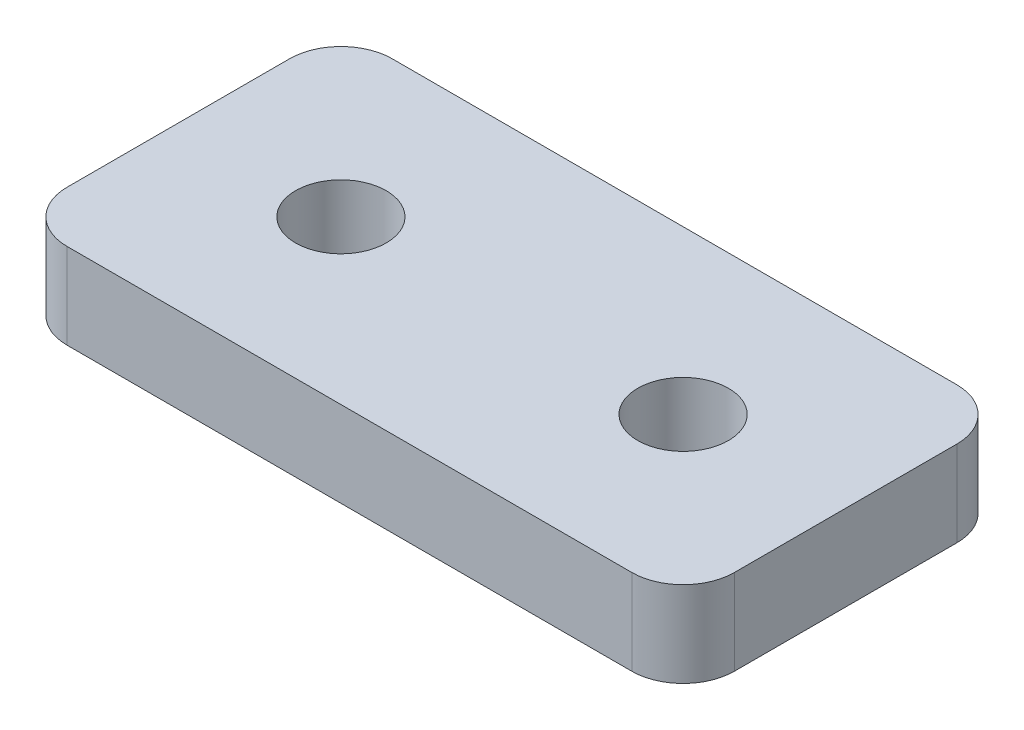
SolidWorks part; units mm, degrees
ref_plane "Top" through (0, 0, 0) normal (0, 0, 1) x (1, 0, 0)
ref_plane "Front" through (0, 0, 0) normal (0, 1, 0) x (1, 0, 0)
ref_plane "Right" through (0, 0, 0) normal (1, 0, 0) x (0, 0, -1)
sketch "2 Hole Profile Sketch" plane through (0, 0, 0) normal (0, 1, 0) x (1, 0, 0)
  line L0 (0, -10) -> (0, 10) construction
  line L1 (-16.5, -9.5) -> (16.5, -9.5)
  line L2 (-19.5, -6.5) -> (-19.5, 6.5)
  line L3 (-16.5, 9.5) -> (16.5, 9.5)
  line L4 (19.5, -6.5) -> (19.5, 6.5)
  line L5 (-20, -10) -> (20, -10) construction
  line L6 (-20, -10) -> (-20, 10) construction
  line L7 (-20, 10) -> (20, 10) construction
  line L8 (20, -10) -> (20, 10) construction
  arc A0 (-16.5, -9.5) -> (-19.5, -6.5) centre (-16.5, -6.5) cw
  arc A1 (-16.5, 9.5) -> (-19.5, 6.5) centre (-16.5, 6.5) ccw
  arc A2 (19.5, 6.5) -> (16.5, 9.5) centre (16.5, 6.5) ccw
  arc A3 (16.5, -9.5) -> (19.5, -6.5) centre (16.5, -6.5) ccw
  circle A4 centre (-10, 0) radius 2.65
  circle A5 centre (10, 0) radius 2.65
  point P24 (0, 0)
  dimension "D2" = 0.5
  dimension "D3" = 0.5
  dimension "D4" = 0.5
  dimension "D7" = 10
  dimension "D1" = 3
  dimension "D5" = 0.5
  dimension "D6" = 20
  dimension "D9" = 10
  dimension "D12" = 20
  dimension "D8" = 5.3
  dimension "D11" = 20
extrude "2 Hole Profile" add sketch "2 Hole Profile Sketch" along normal blind 5
sketch "3 Hole Profile Sketch" plane through (0, 0, 0) normal (0, 1, 0) x (1, 0, 0)
  line L0 (0, -10) -> (0, 10) construction
  line L1 (-16.5, -9.5) -> (36.5, -9.5)
  line L2 (-19.5, -6.5) -> (-19.5, 6.5)
  line L3 (-16.5, 9.5) -> (36.5, 9.5)
  line L4 (39.5, -6.5) -> (39.5, 6.5)
  line L5 (-20, -10) -> (40, -10) construction
  line L6 (-20, -10) -> (-20, 10) construction
  line L7 (-20, 10) -> (40, 10) construction
  line L8 (40, -10) -> (40, 10) construction
  arc A0 (-16.5, -9.5) -> (-19.5, -6.5) centre (-16.5, -6.5) cw
  arc A1 (-16.5, 9.5) -> (-19.5, 6.5) centre (-16.5, 6.5) ccw
  arc A2 (39.5, 6.5) -> (36.5, 9.5) centre (36.5, 6.5) ccw
  arc A3 (36.5, -9.5) -> (39.5, -6.5) centre (36.5, -6.5) ccw
  circle A4 centre (-10, 0) radius 2.65
  circle A5 centre (10, 0) radius 2.65
  circle A6 centre (30, 0) radius 2.65
  point P29 (0, 0)
  dimension "D2" = 0.5
  dimension "D3" = 0.5
  dimension "D4" = 0.5
  dimension "D10" = 20
  dimension "D7" = 10
  dimension "D1" = 3
  dimension "D8" = 5.3
  dimension "D5" = 0.5
  dimension "D6" = 20
  dimension "D9" = 10
  dimension "D11" = 40
  dimension "D12" = 20
extrude "3 Hole Thickness Extrude" [suppressed] add sketch "3 Hole Profile Sketch" along normal blind 5
sketch "4 Hole Profile Sketch" plane through (0, 0, 0) normal (0, 1, 0) x (1, 0, 0)
  line L1 (-15.5, -19.5) -> (15.5, -19.5)
  line L2 (-19.5, -15.5) -> (-19.5, 15.5)
  line L3 (-15.5, 19.5) -> (15.5, 19.5)
  line L4 (19.5, -15.5) -> (19.5, 15.5)
  line L5 (0, 19.5) -> (0, -19.5) construction
  line L6 (-19.5, 0) -> (19.5, 0) construction
  line L7 (-20, 20) -> (20, 20) construction
  line L8 (-20, 20) -> (-20, -20) construction
  line L9 (-20, -20) -> (20, -20) construction
  line L10 (20, 20) -> (20, -20) construction
  line L11 (-20, 20) -> (20, -20) construction
  line L12 (-20, -20) -> (20, 20) construction
  circle A0 centre (10, -10) radius 2.65
  circle A1 centre (10, 10) radius 2.65
  circle A2 centre (-9.5, -10) radius 2.65
  circle A3 centre (-9.5, 10) radius 2.65
  arc A4 (-19.5, -15.5) -> (-15.5, -19.5) centre (-15.5, -15.5) ccw
  arc A5 (19.5, -15.5) -> (15.5, -19.5) centre (15.5, -15.5) cw
  arc A6 (15.5, 19.5) -> (19.5, 15.5) centre (15.5, 15.5) cw
  arc A7 (-19.5, 15.5) -> (-15.5, 19.5) centre (-15.5, 15.5) cw
  point P14 (0, 0)
  point P22 (-25, -26)
  point P144 (0, 0)
  dimension "Corner Radius" = 4
  dimension "D9" = 5.3
  dimension "D5" = 10
  dimension "D6" = 10
  dimension "D7" = 10
  dimension "D8" = 10
  dimension "D1" = 40
  dimension "D2" = 0.5
  dimension "D3" = 0.5
  dimension "D4" = 0.5
  dimension "D10" = 20
extrude "4 Hole Thickness Extrude" [suppressed] add sketch "4 Hole Profile Sketch" along normal blind 5
sketch "6 Hole Extension Sketch" plane through (0, 0, 0) normal (0, 1, 0) x (1, 0, 0)
  line L0 (39.5, -15.5) -> (39.5, 15.5)
  line L1 (-20, -19.5) -> (15.5, -19.5) construction
  line L2 (-20, -19.5) -> (-20, 19.5) construction
  line L3 (-20, 19.5) -> (15.5, 19.5) construction
  line L4 (19.5, -15.5) -> (19.5, 15.5)
  line L5 (0, 19.5) -> (0, -19.5) construction
  line L6 (-20, 0) -> (19.5, 0) construction
  line L7 (15.5, -19.5) -> (35.5, -19.5)
  line L8 (15.5, 19.5) -> (35.5, 19.5)
  arc A8 (39.5, -15.5) -> (35.5, -19.5) centre (35.5, -15.5) cw
  arc A9 (35.5, 19.5) -> (39.5, 15.5) centre (35.5, 15.5) cw
  arc A10 (19.5, -15.5) -> (15.5, -19.5) centre (15.5, -15.5) cw
  arc A11 (19.5, 15.5) -> (15.5, 19.5) centre (15.5, 15.5) ccw
  circle A12 centre (29.5, -10) radius 2.65
  circle A13 centre (29.5, 10) radius 2.65
  point P18 (-22.5, -23)
  point P27 (0, 0)
  dimension "Corner Radius" = 4
  dimension "D5" = 5.3
  dimension "D1" = 19.5
  dimension "D2" = 20
  dimension "D6" = 39
  dimension "D3" = 10
  dimension "D4" = 10
  dimension "D7" = 10
  dimension "D8" = 20
extrude "6 Hole Extension Extrude" [suppressed] add sketch "6 Hole Extension Sketch" along normal up to surface (5 mm away) up to face at (0, 5, 0)
equation "\"M5 Close Fit Hole\"= 5.3mm"
equation "\"D9@4 Hole Profile Sketch\" = \"M5 Close Fit Hole\""
equation "\"D5@6 Hole Extension Sketch\" = \"M5 Close Fit Hole\""
equation "\"Clearance\"= 0.5mm"
equation "\"D2@4 Hole Profile Sketch\"=\"Clearance\""
equation "\"D3@4 Hole Profile Sketch\"=\"Clearance\""
equation "\"D4@4 Hole Profile Sketch\"=\"Clearance\""
equation "\"D6@6 Hole Extension Sketch\"=40-2*\"Clearance\""
equation "\"D1@6 Hole Extension Sketch\"=20-\"Clearance\""
equation "\"D2@3 Hole Profile Sketch\" = \"Clearance\""
equation "\"D3@3 Hole Profile Sketch\" = \"Clearance\""
equation "\"D4@3 Hole Profile Sketch\" = \"Clearance\""
equation "\"D5@3 Hole Profile Sketch\" = \"Clearance\""
equation "\"D8@3 Hole Profile Sketch\" = \"M5 Close Fit Hole\""
equation "\"Plate Thickness\"= 5"
equation "\"D1@4 Hole Thickness Extrude\"=\"Plate Thickness\""
equation "\"D1@3 Hole Thickness Extrude\"=\"Plate Thickness\""
equation "\"D8@2 Hole Profile Sketch\" = \"M5 Close Fit Hole\""
equation "\"D1@2 Hole Profile\" = \"Plate Thickness\""
